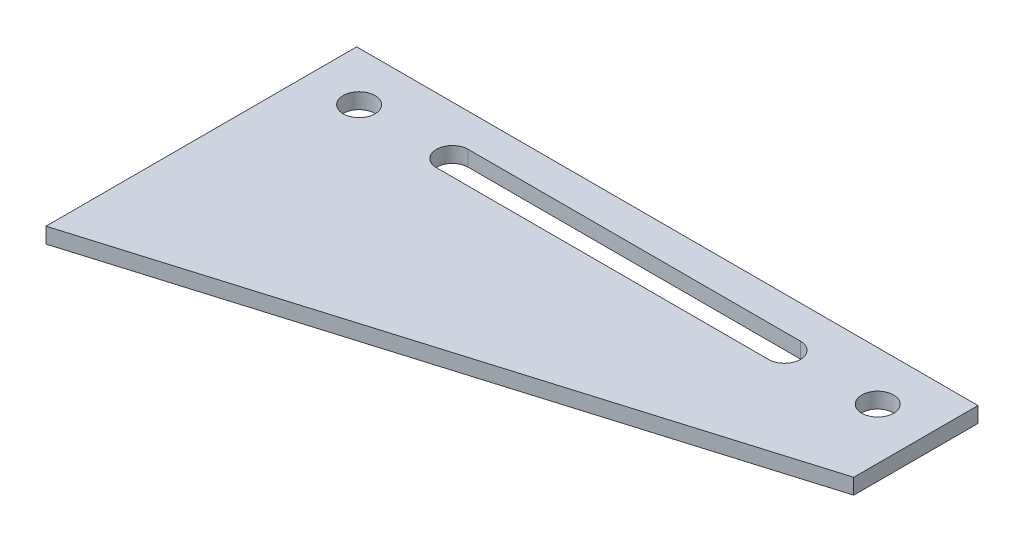
SolidWorks part; units mm, degrees
material "AISI 4130 Steel, annealed at 865C"
ref_plane "X-Y Datum" through (0, 0, 0) normal (0, 0, 1) x (1, 0, 0)
ref_plane "X-Z Datum" through (0, 0, 0) normal (0, 1, 0) x (1, 0, 0)
ref_plane "Y-Z Datum" through (0, 0, 0) normal (1, 0, 0) x (0, 0, -1)
sketch "Sketch1" plane through (0, 0, 0) normal (0, 1, 0) x (1, 0, 0)
  line L0 (0, 38.1) -> (0, -88.9)
  line L1 (-63.5, -88.9) -> (63.5, -88.9)
  line L2 (-63.5, -88.9) -> (-63.5, 38.1)
  line L3 (-63.5, 38.1) -> (63.5, 38.1)
  line L4 (63.5, -88.9) -> (63.5, 38.1)
  point P0 (0, 0)
  dimension "D1" = 127
  dimension "D2" = 38.1
  dimension "D3" = 127
extrude "Boss-Extrude1" add sketch "Sketch1" along normal blind 3.175 contours L3 L4 L1 L2
sketch "Sketch2" plane through (0, 3.175, 0) normal (0, 1, 0) x (1, 0, 0)
  line L0 (-63.5, -25.4) -> (63.5, 12.7)
  line L1 (-53, 31.35) -> (-53, 24.85) construction
  line L2 (-33.95, 31.35) -> (33.95, 31.35) construction
  line L3 (-33.95, 31.35) -> (-33.95, 24.85) construction
  line L4 (-63.5, 38.1) -> (-63.5, -88.9)
  line L5 (-63.5, -88.9) -> (63.5, -88.9)
  line L6 (63.5, -88.9) -> (63.5, 38.1)
  line L7 (63.5, 38.1) -> (-63.5, 38.1)
  line L8 (-63.5, 38.1) -> (-63.5, -88.9)
  line L9 (-63.5, -88.9) -> (63.5, -88.9)
  line L10 (63.5, -88.9) -> (63.5, 38.1)
  line L11 (63.5, 38.1) -> (-63.5, 38.1)
  line L12 (-33.95, 24.85) -> (33.95, 24.85) construction
  line L13 (33.95, 31.35) -> (33.95, 24.85) construction
  line L14 (-33.95, 31.35) -> (33.95, 24.85) construction
  line L15 (-33.95, 24.85) -> (33.95, 31.35) construction
  line L16 (-33.95, 28.1) -> (33.95, 28.1) construction
  line L17 (-33.95, 31.35) -> (33.95, 31.35)
  line L18 (-33.95, 24.85) -> (33.95, 24.85)
  line L19 (-37.2, 28.1) -> (37.2, 28.1) construction
  circle A0 centre (53, 28.1) radius 3.25 construction
  circle A1 centre (-53, 28.1) radius 3.25 construction
  circle A2 centre (53, 28.1) radius 3.25
  circle A3 centre (-53, 28.1) radius 3.25
  arc A4 (-33.95, 31.35) -> (-33.95, 24.85) centre (-33.95, 28.1) ccw
  arc A5 (33.95, 24.85) -> (33.95, 31.35) centre (33.95, 28.1) ccw
  point P6 (0, 28.1)
  point P19 (0, 28.1)
  line M5 (-63.5, 38.1) -> (-63.5, -88.9)
  line M6 (-63.5, -88.9) -> (63.5, -88.9)
  line M7 (63.5, -88.9) -> (63.5, 38.1)
  dimension "D2" = 63.5
  dimension "D3" = 25.4
  dimension "D4" = 19.05
  dimension "D5" = 19.05
  dimension "D1" = 0
extrude "Cut-Extrude1" cut sketch "Sketch2" against normal through all contours L0 M5 M6 M7 | L18 A5 L17 A4 | A2 | A3 region at (4.8846, 3.175, 46.8923) region at (0, 3.175, -28.1) region at (53, 3.175, -28.1) region at (-53, 3.175, -28.1)
